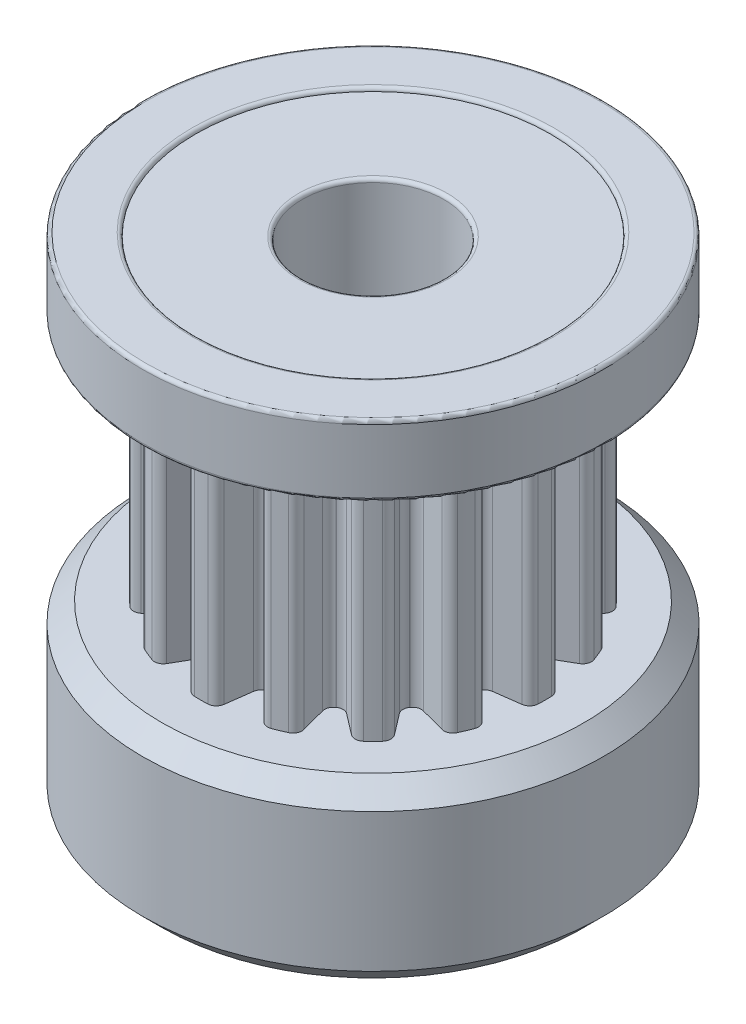
SolidWorks part; units mm, degrees
material "AISI 304"
ref_plane "Front Plane" through (0, 0, 0) normal (0, 0, 1) x (1, 0, 0)
ref_plane "Top Plane" through (0, 0, 0) normal (0, 1, 0) x (1, 0, 0)
ref_plane "Right Plane" through (0, 0, 0) normal (1, 0, 0) x (0, 0, -1)
sketch "Sketch1" plane through (0, 0, 0) normal (0, 1, 0) x (1, 0, 0)
  circle A0 centre (0, 0) radius 6.5
  dimension "D1" = 13
extrude "Boss-Extrude1" add sketch "Sketch1" along normal blind 5
sketch "Sketch2" plane through (0, 5, 0) normal (0, 1, 0) x (1, 0, 0)
  line L0 (0, 6.9554) -> (0, -7.0255) construction
  line L1 (-0.4272, 4.6296) -> (-0.5257, 3.8914)
  line L2 (0.4272, 4.6296) -> (0.5257, 3.8914)
  line L3 (1.377, 4.4407) -> (1.0035, 3.7964)
  line L4 (2.1664, 4.1137) -> (1.9749, 3.394)
  line L5 (2.9715, 3.5757) -> (2.3799, 3.1234)
  line L6 (3.5757, 2.9715) -> (3.1234, 2.3799)
  line L7 (4.1137, 2.1664) -> (3.394, 1.9749)
  line L8 (4.4407, 1.377) -> (3.7964, 1.0035)
  line L9 (4.6296, 0.4272) -> (3.8914, 0.5257)
  line L10 (4.6296, -0.4272) -> (3.8914, -0.5257)
  line L11 (4.4407, -1.377) -> (3.7964, -1.0035)
  line L12 (4.1137, -2.1664) -> (3.394, -1.9749)
  line L13 (3.5757, -2.9715) -> (3.1234, -2.3799)
  line L14 (2.9715, -3.5757) -> (2.3799, -3.1234)
  line L15 (2.1664, -4.1137) -> (1.9749, -3.394)
  line L16 (1.377, -4.4407) -> (1.0035, -3.7964)
  line L17 (0.4272, -4.6296) -> (0.5257, -3.8914)
  line L18 (-0.4272, -4.6296) -> (-0.5257, -3.8914)
  line L19 (-1.377, -4.4407) -> (-1.0035, -3.7964)
  line L20 (-2.1664, -4.1137) -> (-1.9749, -3.394)
  line L21 (-2.9715, -3.5757) -> (-2.3799, -3.1234)
  line L22 (-3.5757, -2.9715) -> (-3.1234, -2.3799)
  line L23 (-4.1137, -2.1664) -> (-3.394, -1.9749)
  line L24 (-4.4407, -1.377) -> (-3.7964, -1.0035)
  line L25 (-4.6296, -0.4272) -> (-3.8914, -0.5257)
  line L26 (-4.6296, 0.4272) -> (-3.8914, 0.5257)
  line L27 (-4.4407, 1.377) -> (-3.7964, 1.0035)
  line L28 (-4.1137, 2.1664) -> (-3.394, 1.9749)
  line L29 (-3.5757, 2.9715) -> (-3.1234, 2.3799)
  line L30 (-2.9715, 3.5757) -> (-2.3799, 3.1234)
  line L31 (-2.1664, 4.1137) -> (-1.9749, 3.394)
  line L32 (-1.377, 4.4407) -> (-1.0035, 3.7964)
  line L33 (-0.738, 3.6767) -> (-0.7252, 3.6792)
  line L34 (0.7252, 3.6792) -> (0.738, 3.6767)
  line L35 (2.0779, 3.1216) -> (2.0888, 3.1144)
  line L36 (3.1144, 2.0888) -> (3.1216, 2.0779)
  line L37 (3.6767, 0.738) -> (3.6792, 0.7252)
  line L38 (3.6792, -0.7252) -> (3.6767, -0.738)
  line L39 (3.1216, -2.0779) -> (3.1144, -2.0888)
  line L40 (2.0888, -3.1144) -> (2.0779, -3.1216)
  line L41 (0.738, -3.6767) -> (0.7252, -3.6792)
  line L42 (-0.7252, -3.6792) -> (-0.738, -3.6767)
  line L43 (-2.0779, -3.1216) -> (-2.0888, -3.1144)
  line L44 (-3.1144, -2.0888) -> (-3.1216, -2.0779)
  line L45 (-3.6767, -0.738) -> (-3.6792, -0.7252)
  line L46 (-3.6792, 0.7252) -> (-3.6767, 0.738)
  line L47 (-3.1216, 2.0779) -> (-3.1144, 2.0888)
  line L48 (-2.0888, 3.1144) -> (-2.0779, 3.1216)
  arc A0 (0.1892, 4.8463) -> (-0.1892, 4.8463) centre (0, 0) ccw
  arc A2 (0.4272, 4.6296) -> (0.1892, 4.8463) centre (0.1794, 4.5965) ccw
  arc A3 (-0.4272, 4.6296) -> (-0.1892, 4.8463) centre (-0.1794, 4.5965) cw
  arc A4 (0.5257, 3.8914) -> (0.7252, 3.6792) centre (0.7735, 3.9245) ccw
  arc A5 (-0.5257, 3.8914) -> (-0.7252, 3.6792) centre (-0.7735, 3.9245) cw
  arc A6 (2.0294, 4.405) -> (1.6798, 4.5498) centre (0, 0) ccw
  arc A7 (2.1664, 4.1137) -> (2.0294, 4.405) centre (1.9248, 4.178) ccw
  arc A8 (1.377, 4.4407) -> (1.6798, 4.5498) centre (1.5933, 4.3153) cw
  arc A9 (1.9749, 3.394) -> (2.0779, 3.1216) centre (2.2165, 3.3297) ccw
  arc A10 (1.0035, 3.7964) -> (0.738, 3.6767) centre (0.7872, 3.9218) cw
  arc A11 (3.5606, 3.2931) -> (3.2931, 3.5606) centre (0, 0) ccw
  arc A12 (3.5757, 2.9715) -> (3.5606, 3.2931) centre (3.3771, 3.1234) ccw
  arc A13 (2.9715, 3.5757) -> (3.2931, 3.5606) centre (3.1234, 3.3771) cw
  arc A14 (3.1234, 2.3799) -> (3.1144, 2.0888) centre (3.322, 2.2281) ccw
  arc A15 (2.3799, 3.1234) -> (2.0888, 3.1144) centre (2.2281, 3.322) cw
  arc A16 (4.5498, 1.6798) -> (4.405, 2.0294) centre (0, 0) ccw
  arc A17 (4.4407, 1.377) -> (4.5498, 1.6798) centre (4.3153, 1.5933) ccw
  arc A18 (4.1137, 2.1664) -> (4.405, 2.0294) centre (4.178, 1.9248) cw
  arc A19 (3.7964, 1.0035) -> (3.6767, 0.738) centre (3.9218, 0.7872) ccw
  arc A20 (3.394, 1.9749) -> (3.1216, 2.0779) centre (3.3297, 2.2165) cw
  arc A21 (4.8463, -0.1892) -> (4.8463, 0.1892) centre (0, 0) ccw
  arc A22 (4.6296, -0.4272) -> (4.8463, -0.1892) centre (4.5965, -0.1794) ccw
  arc A23 (4.6296, 0.4272) -> (4.8463, 0.1892) centre (4.5965, 0.1794) cw
  arc A24 (3.8914, -0.5257) -> (3.6792, -0.7252) centre (3.9245, -0.7735) ccw
  arc A25 (3.8914, 0.5257) -> (3.6792, 0.7252) centre (3.9245, 0.7735) cw
  arc A26 (4.405, -2.0294) -> (4.5498, -1.6798) centre (0, 0) ccw
  arc A27 (4.1137, -2.1664) -> (4.405, -2.0294) centre (4.178, -1.9248) ccw
  arc A28 (4.4407, -1.377) -> (4.5498, -1.6798) centre (4.3153, -1.5933) cw
  arc A29 (3.394, -1.9749) -> (3.1216, -2.0779) centre (3.3297, -2.2165) ccw
  arc A30 (3.7964, -1.0035) -> (3.6767, -0.738) centre (3.9218, -0.7872) cw
  arc A31 (3.2931, -3.5606) -> (3.5606, -3.2931) centre (0, 0) ccw
  arc A32 (2.9715, -3.5757) -> (3.2931, -3.5606) centre (3.1234, -3.3771) ccw
  arc A33 (3.5757, -2.9715) -> (3.5606, -3.2931) centre (3.3771, -3.1234) cw
  arc A34 (2.3799, -3.1234) -> (2.0888, -3.1144) centre (2.2281, -3.322) ccw
  arc A35 (3.1234, -2.3799) -> (3.1144, -2.0888) centre (3.322, -2.2281) cw
  arc A36 (1.6798, -4.5498) -> (2.0294, -4.405) centre (0, 0) ccw
  arc A37 (1.377, -4.4407) -> (1.6798, -4.5498) centre (1.5933, -4.3153) ccw
  arc A38 (2.1664, -4.1137) -> (2.0294, -4.405) centre (1.9248, -4.178) cw
  arc A39 (1.0035, -3.7964) -> (0.738, -3.6767) centre (0.7872, -3.9218) ccw
  arc A40 (1.9749, -3.394) -> (2.0779, -3.1216) centre (2.2165, -3.3297) cw
  arc A41 (-0.1892, -4.8463) -> (0.1892, -4.8463) centre (0, 0) ccw
  arc A42 (-0.4272, -4.6296) -> (-0.1892, -4.8463) centre (-0.1794, -4.5965) ccw
  arc A43 (0.4272, -4.6296) -> (0.1892, -4.8463) centre (0.1794, -4.5965) cw
  arc A44 (-0.5257, -3.8914) -> (-0.7252, -3.6792) centre (-0.7735, -3.9245) ccw
  arc A45 (0.5257, -3.8914) -> (0.7252, -3.6792) centre (0.7735, -3.9245) cw
  arc A46 (-2.0294, -4.405) -> (-1.6798, -4.5498) centre (0, 0) ccw
  arc A47 (-2.1664, -4.1137) -> (-2.0294, -4.405) centre (-1.9248, -4.178) ccw
  arc A48 (-1.377, -4.4407) -> (-1.6798, -4.5498) centre (-1.5933, -4.3153) cw
  arc A49 (-1.9749, -3.394) -> (-2.0779, -3.1216) centre (-2.2165, -3.3297) ccw
  arc A50 (-1.0035, -3.7964) -> (-0.738, -3.6767) centre (-0.7872, -3.9218) cw
  arc A51 (-3.5606, -3.2931) -> (-3.2931, -3.5606) centre (0, 0) ccw
  arc A52 (-3.5757, -2.9715) -> (-3.5606, -3.2931) centre (-3.3771, -3.1234) ccw
  arc A53 (-2.9715, -3.5757) -> (-3.2931, -3.5606) centre (-3.1234, -3.3771) cw
  arc A54 (-3.1234, -2.3799) -> (-3.1144, -2.0888) centre (-3.322, -2.2281) ccw
  arc A55 (-2.3799, -3.1234) -> (-2.0888, -3.1144) centre (-2.2281, -3.322) cw
  arc A56 (-4.5498, -1.6798) -> (-4.405, -2.0294) centre (0, 0) ccw
  arc A57 (-4.4407, -1.377) -> (-4.5498, -1.6798) centre (-4.3153, -1.5933) ccw
  arc A58 (-4.1137, -2.1664) -> (-4.405, -2.0294) centre (-4.178, -1.9248) cw
  arc A59 (-3.7964, -1.0035) -> (-3.6767, -0.738) centre (-3.9218, -0.7872) ccw
  arc A60 (-3.394, -1.9749) -> (-3.1216, -2.0779) centre (-3.3297, -2.2165) cw
  arc A61 (-4.8463, 0.1892) -> (-4.8463, -0.1892) centre (0, 0) ccw
  arc A62 (-4.6296, 0.4272) -> (-4.8463, 0.1892) centre (-4.5965, 0.1794) ccw
  arc A63 (-4.6296, -0.4272) -> (-4.8463, -0.1892) centre (-4.5965, -0.1794) cw
  arc A64 (-3.8914, 0.5257) -> (-3.6792, 0.7252) centre (-3.9245, 0.7735) ccw
  arc A65 (-3.8914, -0.5257) -> (-3.6792, -0.7252) centre (-3.9245, -0.7735) cw
  arc A66 (-4.405, 2.0294) -> (-4.5498, 1.6798) centre (0, 0) ccw
  arc A67 (-4.1137, 2.1664) -> (-4.405, 2.0294) centre (-4.178, 1.9248) ccw
  arc A68 (-4.4407, 1.377) -> (-4.5498, 1.6798) centre (-4.3153, 1.5933) cw
  arc A69 (-3.394, 1.9749) -> (-3.1216, 2.0779) centre (-3.3297, 2.2165) ccw
  arc A70 (-3.7964, 1.0035) -> (-3.6767, 0.738) centre (-3.9218, 0.7872) cw
  arc A71 (-3.2931, 3.5606) -> (-3.5606, 3.2931) centre (0, 0) ccw
  arc A72 (-2.9715, 3.5757) -> (-3.2931, 3.5606) centre (-3.1234, 3.3771) ccw
  arc A73 (-3.5757, 2.9715) -> (-3.5606, 3.2931) centre (-3.3771, 3.1234) cw
  arc A74 (-2.3799, 3.1234) -> (-2.0888, 3.1144) centre (-2.2281, 3.322) ccw
  arc A75 (-3.1234, 2.3799) -> (-3.1144, 2.0888) centre (-3.322, 2.2281) cw
  arc A76 (-1.6798, 4.5498) -> (-2.0294, 4.405) centre (0, 0) ccw
  arc A77 (-1.377, 4.4407) -> (-1.6798, 4.5498) centre (-1.5933, 4.3153) ccw
  arc A78 (-2.1664, 4.1137) -> (-2.0294, 4.405) centre (-1.9248, 4.178) cw
  arc A79 (-1.0035, 3.7964) -> (-0.738, 3.6767) centre (-0.7872, 3.9218) ccw
  arc A80 (-1.9749, 3.394) -> (-2.0779, 3.1216) centre (-2.2165, 3.3297) cw
  point P12 (0.4, 4.8335)
  point P15 (-0.4, 4.8335)
  point P17 (0.55, 3.7094)
  point P20 (-0.55, 3.7094)
  point P203 (0, 0)
  point P233 (0, 0)
  dimension "D1" = 9.7
  dimension "D2" = 16
  dimension "D5" = 0.25
  dimension "D6" = 0.25
  dimension "D3" = 0.4
  dimension "D4" = 0.55
  dimension "D7" = 16
extrude "Boss-Extrude2" add sketch "Sketch2" along normal blind 7
sketch "Sketch3" plane through (0, 12, 0) normal (0, 1, 0) x (1, 0, 0)
  circle A0 centre (0, 0) radius 6.5
  dimension "D1" = 13
extrude "Boss-Extrude3" add sketch "Sketch3" along normal blind 2
sketch "Sketch4" plane through (0, 14, 0) normal (0, 1, 0) x (1, 0, 0)
  circle A0 centre (0, 0) radius 2
  dimension "D1" = 4
extrude "Cut-Extrude1" cut sketch "Sketch4" against normal through all
sketch "Sketch5" plane through (0, 14, 0) normal (0, 1, 0) x (1, 0, 0)
  circle A0 centre (0, 0) radius 2
  circle A1 centre (0, 0) radius 5
  dimension "D1" = 4
  dimension "D2" = 10
extrude "Cut-Extrude2" cut sketch "Sketch5" against normal blind 0.1
fillet "Fillet1" radius 0.1 4 edges at (0, 12, 6.5) (0, 13.9, 2) (0, 14, 5) (0, 14, 6.5)
chamfer "Chamfer1" distance 0.55 angle 45 2 edges at (0, 0, 6.5) (0, 5, 6.5)
sketch "Sketch6" plane through (0, 0, 0) normal (0, 0, 1) x (1, 0, 0)
  line L0 (0, 0) -> (0, 5) construction
  line L1 (5.95, 5) -> (-5.95, 5) construction
  circle A0 centre (0, 2.5) radius 1.25
  dimension "D1" = 2.5
extrude "Cut-Extrude3" cut sketch "Sketch6" against normal through all
cosmetic thread "Cosmetic Thread1" parameters "D2"=3
sketch "Sketch7" plane through (0, 0, 0) normal (1, 0, 0) x (0, 0, -1)
  line L0 (0, -0.4275) -> (0, 5.6101) construction
  line L1 (-5.95, 0) -> (5.95, 0) construction
  circle A0 centre (0, 2.5) radius 1.25
  dimension "D1" = 2.5
  dimension "D2" = 2.5
extrude "Cut-Extrude4" cut sketch "Sketch7" against normal through all
cosmetic thread "Cosmetic Thread2" parameters "D2"=3
